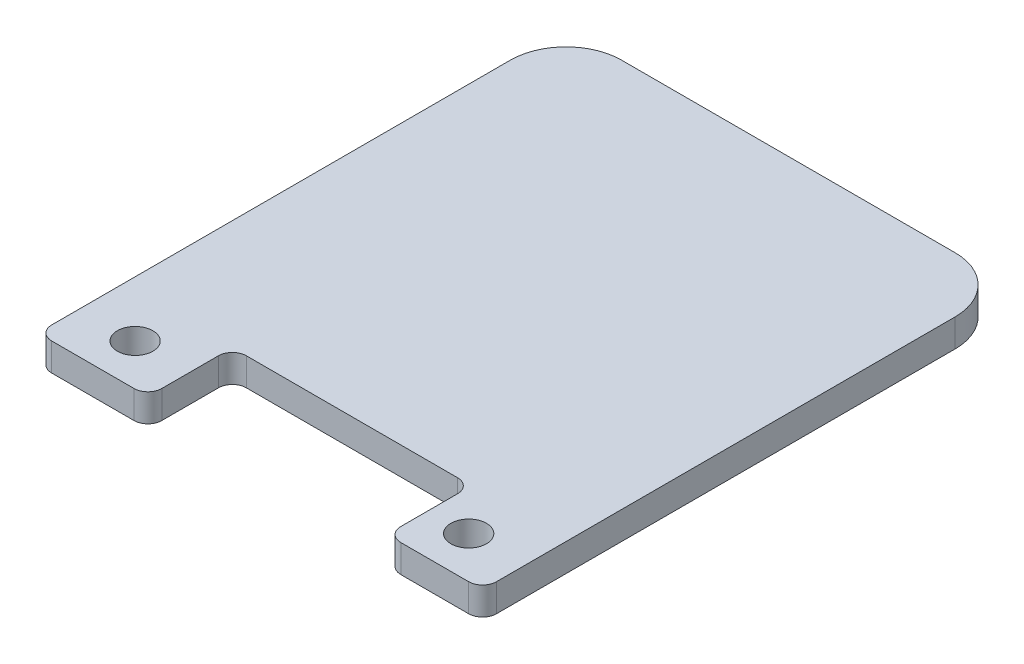
SolidWorks part; units mm, degrees
ref_plane "Front Plane" through (0, 0, 0) normal (0, 0, 1) x (1, 0, 0)
ref_plane "Top Plane" through (0, 0, 0) normal (0, 1, 0) x (1, 0, 0)
ref_plane "Right Plane" through (0, 0, 0) normal (1, 0, 0) x (0, 0, -1)
sketch "Sketch1" plane through (0, 0, 0) normal (0, 1, 0) x (1, 0, 0)
  line L1 (-25.4, 30.1625) -> (25.4, 30.1625)
  line L2 (-25.4, 30.1625) -> (-25.4, -30.1625)
  line L3 (-25.4, -30.1625) -> (25.4, -30.1625)
  line L4 (25.4, 30.1625) -> (25.4, -30.1625)
  line L5 (-25.4, 30.1625) -> (25.4, -30.1625) construction
  line L6 (-25.4, -30.1625) -> (25.4, 30.1625) construction
  point P0 (0, 0)
  dimension "D1" = 50.8
  dimension "D2" = 60.325
extrude "Boss-Extrude1" add sketch "Sketch1" along normal blind 3.175
sketch "Sketch2" plane through (0, 0, 0) normal (0, -1, 0) x (-1, 0, 0)
  line L0 (25.4, -30.1625) -> (-25.4, -30.1625) construction
  line L1 (-19.05, -25.4) -> (-25.4, -25.4) construction
  line L2 (-25.4, -30.1625) -> (-25.4, 30.1625) construction
  line L3 (19.05, -25.4) -> (25.4, -25.4) construction
  line L4 (25.4, 30.1625) -> (25.4, -30.1625) construction
  circle A0 centre (-19.05, -25.4) radius 2.032
  circle A1 centre (19.05, -25.4) radius 2.032
  dimension "D2" = 4.064
  dimension "D1" = 4.7625
  dimension "D3" = 38.1
extrude "Cut-Extrude1" cut sketch "Sketch2" against normal through all
sketch "Sketch3" plane through (0, 3.175, 0) normal (0, 1, 0) x (1, 0, 0)
  line L0 (-25.4, -30.1625) -> (25.4, -30.1625) construction
  line L1 (-12.827, -30.1625) -> (14.478, -30.1625)
  line L2 (-12.827, -30.1625) -> (-12.827, -20.5105)
  line L3 (-12.827, -20.5105) -> (14.478, -20.5105)
  line L4 (14.478, -30.1625) -> (14.478, -20.5105)
  line L5 (-25.4, 30.1625) -> (-25.4, -30.1625) construction
  dimension "D1" = 12.573
  dimension "D2" = 27.305
  dimension "D3" = 9.652
extrude "Cut-Extrude2" cut sketch "Sketch3" against normal through all
fillet "Fillet1" radius 1.5875 6 edges at (-25.4, 1.5875, 30.1625) (-12.827, 1.5875, 30.1625) (-12.827, 1.5875, 20.5105) (14.478, 1.5875, 20.5105) (14.478, 1.5875, 30.1625) (25.4, 1.5875, 30.1625)
fillet "Fillet2" radius 6.35 2 edges at (-25.4, 1.5875, -30.1625) (25.4, 1.5875, -30.1625)
